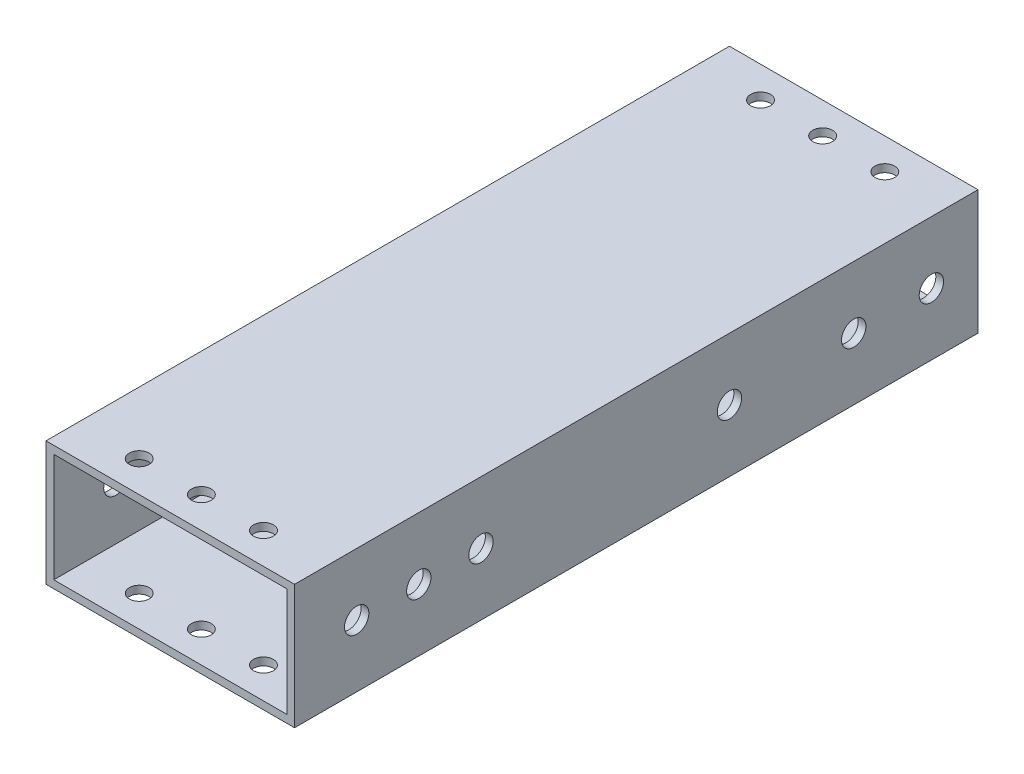
SolidWorks part; units mm, degrees
material "6061-T6 (SS)"
ref_plane "Front Plane" through (0, 0, 0) normal (0, 0, 1) x (1, 0, 0)
ref_plane "Top Plane" through (0, 0, 0) normal (0, 1, 0) x (1, 0, 0)
ref_plane "Right Plane" through (0, 0, 0) normal (1, 0, 0) x (0, 0, -1)
sketch "Sketch1" plane through (0, 0, 0) normal (0, 0, 1) x (1, 0, 0)
  line L0 (-23.8125, 11.1125) -> (23.8125, 11.1125)
  line L1 (-25.4, -12.7) -> (25.4, -12.7)
  line L2 (-25.4, -12.7) -> (-25.4, 12.7)
  line L3 (-25.4, 12.7) -> (25.4, 12.7)
  line L4 (25.4, -12.7) -> (25.4, 12.7)
  line L5 (-25.4, -12.7) -> (25.4, 12.7) construction
  line L6 (-25.4, 12.7) -> (25.4, -12.7) construction
  line L7 (23.8125, -11.1125) -> (23.8125, 11.1125)
  line L8 (-23.8125, -11.1125) -> (23.8125, -11.1125)
  line L9 (-23.8125, -11.1125) -> (-23.8125, 11.1125)
  point P0 (0, 0)
  dimension "D1" = 50.8
  dimension "D2" = 25.4
  dimension "D3" = 1.5875
extrude "Boss-Extrude1" add sketch "Sketch1" along normal mid plane 139.7
sketch "Sketch2" plane through (0, 12.7, 0) normal (0, 1, 0) x (1, 0, 0)
  line L0 (25.4, 69.85) -> (-25.4, 69.85) construction
  line L1 (25.4, 0) -> (-25.4, 0) construction
  line L2 (25.4, -69.85) -> (25.4, 69.85) construction
  line L3 (-25.4, -69.85) -> (-25.4, 69.85) construction
  circle A0 centre (-12.7, 63.5) radius 2.0193
  circle A1 centre (0, 63.5) radius 2.0193
  circle A2 centre (12.7, 63.5) radius 2.0193
  circle A3 centre (12.7, -63.5) radius 2.0193
  circle A4 centre (0, -63.5) radius 2.0193
  circle A5 centre (-12.7, -63.5) radius 2.0193
  dimension "D1" = 4.0386
  dimension "D2" = 12.7
  dimension "D3" = 12.7
  dimension "D4" = 6.35
extrude "Cut-Extrude1" cut sketch "Sketch2" against normal through all
sketch "Sketch3" plane through (25.4, 0, 0) normal (1, 0, 0) x (0, 0, -1)
  line L0 (0, 12.7) -> (0, -12.7) construction
  line L1 (-69.85, 12.7) -> (69.85, 12.7) construction
  line L2 (-69.85, -12.7) -> (69.85, -12.7) construction
  line L3 (-69.85, -12.7) -> (-69.85, 12.7) construction
  line L5 (69.85, -12.7) -> (69.85, 12.7) construction
  circle A0 centre (-57.15, 0) radius 2.4892
  circle A2 centre (-44.45, 0) radius 2.4892
  circle A3 centre (-31.75, 0) radius 2.4892
  circle A8 centre (60.325, 0) radius 2.4892
  circle A9 centre (44.45, 0) radius 2.4892
  circle A10 centre (19.05, 0) radius 2.4892
  point P23 (0, 0)
  point P24 (0, 0)
  point P25 (45.5496, 3.3868)
  dimension "D1" = 9.525
  dimension "D3" = 4.9784
  dimension "D8" = 4.9784
  dimension "D2" = 12.7
  dimension "D4" = 12.7
  dimension "D5" = 12.7
  dimension "D6" = 15.875
  dimension "D7" = 25.4
extrude "Cut-Extrude2" cut sketch "Sketch3" against normal through all
